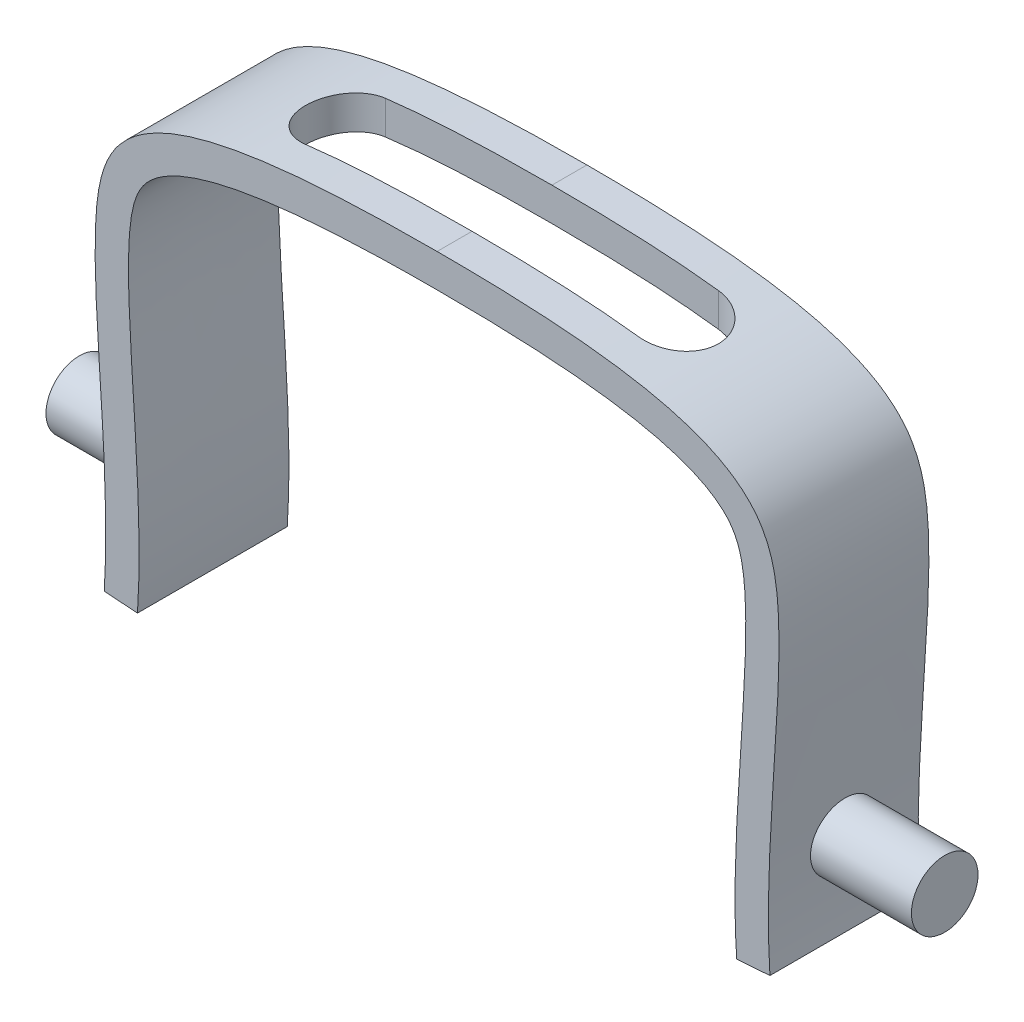
SolidWorks part; units mm, degrees
ref_plane "Front Plane" through (0, 0, 0) normal (0, 0, 1) x (1, 0, 0)
ref_plane "Top Plane" through (0, 0, 0) normal (0, 1, 0) x (1, 0, 0)
ref_plane "Right Plane" through (0, 0, 0) normal (1, 0, 0) x (0, 0, -1)
sketch "Sketch3" plane through (0, 0, 0) normal (0, 0, 1) x (1, 0, 0)
  line L0 (-25.3926, 0.4128) -> (-22.8588, 0.2357)
  line L1 (0, 0) -> (0, 49.1985) construction
  line L2 (22.8588, 0.2357) -> (25.3926, 0.4128)
  spline S0 degree 3 poles (-22.8588, 0.2357) (-22.2073, 9.561) (-24.8571, 24.7477) (-20.4286, 32.2593) (-9.2595, 33.02) (0, 33.02) knots 0 0 0 0 0.433889 0.533889 1 1 1 1
  spline S1 degree 1 poles (-25.3926, 0.4128) (0, 35.56) knots 0 0 1 1 construction
  spline S2 degree 3 poles (22.8588, 0.2357) (22.2073, 9.561) (24.8571, 24.7477) (20.4286, 32.2593) (9.2595, 33.02) (0, 33.02) knots 0 0 0 0 0.433889 0.533889 1 1 1 1
  spline S3 degree 1 poles (25.3926, 0.4128) (0, 35.56) knots 0 0 1 1 construction
  spline S4 degree 3 poles (-25.3926, 0.4128) (-25.3472, 1.0633) (-25.2873, 2.3429) (-25.2559, 5.0926) (-25.3636, 8.6726) (-25.623, 13.0382) (-25.906, 17.2716) (-26.1042, 21.2032) (-26.0979, 24.6856) (-25.8161, 27.1655) (-25.2212, 28.9768) (-24.5105, 30.2231) (-23.5816, 31.2478) (-22.1911, 32.3246) (-20.1914, 33.3182) (-17.4516, 34.1574) (-13.3644, 34.9503) (-8.7163, 35.3649) (-3.7754, 35.5373) (-1.2543, 35.56) (0, 35.56) knots 0 0 0 0 0.03125 0.0625 0.125 0.1875 0.25 0.3125 0.375 0.4375 0.46875 0.5 0.53125 0.5625 0.625 0.6875 0.75 0.875 0.9375 1 1 1 1
  spline S5 degree 3 poles (0, 35.56) (1.2543, 35.56) (3.7754, 35.5373) (8.7163, 35.3649) (13.3644, 34.9503) (17.4516, 34.1574) (20.1914, 33.3182) (22.1911, 32.3246) (23.5816, 31.2478) (24.5105, 30.2231) (25.2212, 28.9768) (25.8161, 27.1655) (26.0979, 24.6856) (26.1042, 21.2032) (25.906, 17.2716) (25.623, 13.0382) (25.3636, 8.6726) (25.2559, 5.0926) (25.2873, 2.3429) (25.3472, 1.0633) (25.3926, 0.4128) knots 0 0 0 0 0.0625 0.125 0.25 0.3125 0.375 0.4375 0.46875 0.5 0.53125 0.5625 0.625 0.6875 0.75 0.8125 0.875 0.9375 0.96875 1 1 1 1
  dimension "D1" = 22.86
  dimension "D2" = 33.02
  dimension "D3" = 2.54
extrude "main body" add sketch "Sketch3" along normal mid plane 11.43
ref_plane "top of rounded bit" through (0, 35.56, 0) normal (0, 1, 0) x (1, 0, 0)
sketch "Sketch4" plane through (0, 35.56, 0) normal (0, 1, 0) x (1, 0, 0)
  line L0 (-12.7, 0) -> (12.7, 0) construction
  line L1 (0, -5.715) -> (0, 5.715) construction
  line L2 (-12.7, 3.048) -> (12.7, 3.048)
  line L3 (-12.7, -3.048) -> (12.7, -3.048)
  arc A0 (-12.7, 3.048) -> (-12.7, -3.048) centre (-12.7, 0) ccw
  arc A1 (12.7, -3.048) -> (12.7, 3.048) centre (12.7, 0) ccw
  point P4 (0, 0)
extrude "slot for joystick" cut sketch "Sketch4" against normal blind 127 and the other way blind 127
ref_plane "nibble plane one" through (-25.3926, 0, 0) normal (1, 0, 0) x (0, 0, -1)
ref_plane "nibble plane two" through (25.3926, 0, 0) normal (1, 0, 0) x (0, 0, -1)
sketch "Sketch5" plane through (25.3926, 0, 0) normal (1, 0, 0) x (0, 0, -1)
  line L0 (-5.715, 0.4128) -> (5.715, 0.4128) construction
  circle A0 centre (0, 6.7628) radius 2.54
  point P2 (0, 0.4128)
  dimension "D1" = 6.35
extrude "nibble two" add sketch "Sketch5" along normal blind 7.62 and the other way up to body
sketch "Sketch6" plane through (-25.3926, 0, 0) normal (1, 0, 0) x (0, 0, -1)
  line L0 (-5.715, 0.4128) -> (5.715, 0.4128) construction
  circle A0 centre (0, 6.7628) radius 2.54
  point P2 (0, 0.4128)
  dimension "D1" = 6.35
extrude "nibble one" add sketch "Sketch6" against normal blind 7.62 and the other way up to body
ref_point "nibble center"
ref_plane "nibble flag plane" through (0, 6.7628, 0) normal (0, 1, 0) x (1, 0, 0)
sketch "Sketch7" plane through (0, 6.7628, 0) normal (0, 1, 0) x (1, 0, 0)
  line L1 (-31.3343, 0.6195) -> (-27.5243, 0.6195)
  line L2 (-31.3343, 0.6195) -> (-31.3343, -0.6505)
  line L3 (-31.3343, -0.6505) -> (-27.5243, -0.6505)
  line L4 (-27.5243, 0.6195) -> (-27.5243, -0.6505)
  line L5 (-31.3343, 0.6195) -> (-27.5243, -0.6505) construction
  line L6 (-31.3343, -0.6505) -> (-27.5243, 0.6195) construction
  point P0 (-29.4293, -0.0155)
  dimension "D1" = 1.27
  dimension "D2" = 3.81
extrude "flag" add sketch "Sketch7" against normal blind 0.254
